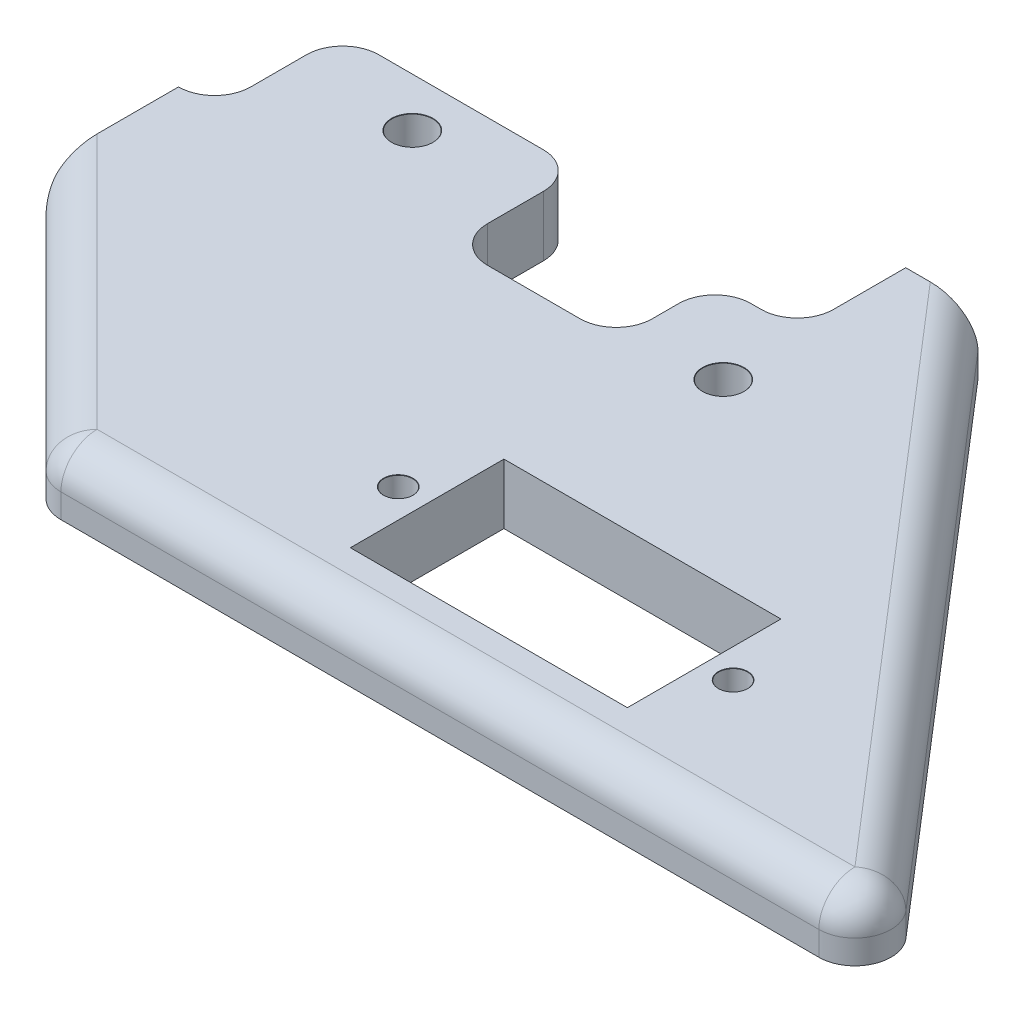
SolidWorks part; units mm, degrees
ref_plane "Front Plane" through (0, 0, 0) normal (0, 0, 1) x (1, 0, 0)
ref_plane "Top Plane" through (0, 0, 0) normal (0, 1, 0) x (1, 0, 0)
ref_plane "Right Plane" through (0, 0, 0) normal (1, 0, 0) x (0, 0, -1)
sketch "Sketch1" plane through (0, 0, 0) normal (0, 1, 0) x (1, 0, 0)
  line L0 (6.83, 0) -> (-6.83, 0)
  line L1 (-9.83, -3) -> (-9.83, -7.63)
  line L2 (9.83, -3) -> (9.83, -7.63)
  line L3 (-12.83, -7.63) -> (-9.83, -7.63) construction
  line L4 (12.83, -7.63) -> (9.83, -7.63) construction
  line L5 (-12.83, -10.63) -> (-12.83, -16.63)
  line L6 (12.83, -10.63) -> (12.83, -16.63)
  line L7 (-12.83, -16.63) -> (12.83, -16.63)
  arc A0 (-6.83, 0) -> (-9.83, -3) centre (-6.83, -3) ccw
  arc A1 (9.83, -3) -> (6.83, 0) centre (6.83, -3) ccw
  arc A2 (-12.83, -10.63) -> (-9.83, -7.63) centre (-12.83, -7.63) ccw
  arc A3 (9.83, -7.63) -> (12.83, -10.63) centre (12.83, -7.63) ccw
  point P4 (0, 0)
  dimension "D4" = 13.66
  dimension "D1" = 3
  dimension "D2" = 6
  dimension "D3" = 13.66
  dimension "D5" = 4.63
extrude "Boss-Extrude1" add sketch "Sketch1" along normal blind 5
sketch "Sketch2" plane through (0, 5, 0) normal (0, 1, 0) x (1, 0, 0)
  line L0 (-12.83, -16.63) -> (-12.83, -23.63)
  line L1 (-12.83, -23.63) -> (54.3469, -41.63)
  line L2 (54.3469, -41.63) -> (54.3469, -16.63)
  line L3 (54.3469, -16.63) -> (12.83, -16.63)
  line L4 (-12.83, -16.63) -> (12.83, -16.63) construction
  line L5 (-12.83, -16.63) -> (12.83, -16.63)
  dimension "D1" = 25
  dimension "D2" = 7
  dimension "D3" = 75
extrude "Boss-Extrude2" [suppressed] add sketch "Sketch2" against normal up to surface (127 mm away) up to face at (0, 0, 7.578)
sketch "Sketch9" plane through (0, 5, 0) normal (0, 1, 0) x (1, 0, 0)
  line L0 (12.83, -16.63) -> (12.83, -10.63) construction
  line L1 (12.83, -16.63) -> (12.83, -10.63)
  line L2 (12.83, -10.63) -> (20.51, -10.63)
  line L3 (23.51, -7.63) -> (23.51, -5.44)
  line L4 (26.51, -2.44) -> (27.36, -2.44)
  line L5 (30.36, 0.56) -> (30.36, 6.56)
  line L6 (12.83, -16.63) -> (36.36, -16.63)
  line L7 (36.36, -16.63) -> (36.36, 6.56)
  line L8 (36.36, 6.56) -> (30.36, 6.56)
  arc A0 (27.36, -2.44) -> (30.36, 0.56) centre (27.36, 0.56) ccw
  arc A1 (23.51, -5.44) -> (26.51, -2.44) centre (26.51, -5.44) cw
  arc A2 (20.51, -10.63) -> (23.51, -7.63) centre (20.51, -7.63) ccw
  dimension "D1" = 3
  dimension "D2" = 7.68
  dimension "D3" = 2.19
  dimension "D4" = 6
  dimension "D5" = 0.85
  dimension "D6" = 6
extrude "Boss-Extrude3" add sketch "Sketch9" against normal up to surface (5 mm away) up to face at (0, 0, 7.578)
hole_wizard "M3 Clearance Hole2" positions "Sketch7" profile "Sketch8" hole size "M3" standard "ANSI Metric" end condition through all
sketch "Sketch7" plane through (0, 5, 0) normal (0, 1, 0) x (1, 0, 0)
  line L0 (0, -4.05) -> (0, 0) construction
  line L1 (29.4813, -1.5613) -> (30.8213, -1.5613) construction
  line L2 (30.8213, -1.5613) -> (30.8213, -9.0513) construction
  arc A0 (27.36, -2.44) -> (30.36, 0.56) centre (27.36, 0.56) ccw construction
  arc A1 (27.36, -2.44) -> (30.36, 0.56) centre (27.36, 0.56) ccw construction
  point P0 (0, -4.05)
  point P5 (30.8213, -9.0513)
  dimension "D1" = 4.05
  dimension "D2" = 1.34
  dimension "D3" = 7.49
sketch "Sketch8" plane through (0, 5, 4.05) normal (1, 0, 0) x (0, 0, 1)
  line L0 (0, 0) -> (0, 5)
  line L1 (0, 5) -> (1.7, 5)
  line L2 (1.7, 5) -> (1.7, 0.025)
  line L3 (1.7, 0.025) -> (1.725, 0)
  line L5 (1.725, 0) -> (0, 0)
  line L6 (-1.7, 0.025) -> (-1.725, 0) construction
  line L11 (0, -6.35) -> (0, 107.95) construction
  dimension "Thru Hole Dia." = 3.4
  dimension "Thru Hole Depth" = 5
  dimension "Near C'Sink Dia." = 3.45
  dimension "Near C'Sink Angle" = 90
sketch "Sketch10" plane through (0, 5, 0) normal (0, 1, 0) x (1, 0, 0)
  line L0 (0, -4.05) -> (38.94, -4.05) construction
  line L1 (38.94, -4.05) -> (77.88, -4.05) construction
  line L2 (-12.83, -16.63) -> (-12.83, -41.63)
  line L3 (-12.83, -41.63) -> (77.88, -41.63)
  line L4 (36.36, 6.56) -> (77.88, 6.56)
  line L5 (-12.83, -16.63) -> (36.36, -16.63) construction
  line L6 (36.36, -16.63) -> (36.36, 6.56) construction
  line L7 (36.36, -16.63) -> (36.36, 6.56)
  line L8 (-12.83, -16.63) -> (36.36, -16.63)
  line L9 (77.88, 6.56) -> (77.88, -41.63)
  point P7 (0, 0)
  point P9 (-18.83, -47.63)
  dimension "D1" = 38.94
  dimension "D2" = 25
extrude "Boss-Extrude4" add sketch "Sketch10" against normal up to surface (5 mm away) up to face at (0, 0, 5.75)
sketch "Sketch11" plane through (0, 5, 0) normal (0, 1, 0) x (1, 0, 0)
  line L0 (-12.83, -16.63) -> (77.88, -16.63) construction
  line L1 (-12.83, -10.63) -> (-12.83, -41.63) construction
  line L2 (77.88, -41.63) -> (77.88, 6.56) construction
  line L3 (0, -4.05) -> (38.94, -4.05) construction
  line L4 (50.44, -23.88) -> (27.44, -23.88)
  line L5 (50.44, -23.88) -> (50.44, -36.63)
  line L6 (50.44, -36.63) -> (27.44, -36.63)
  line L7 (27.44, -23.88) -> (27.44, -36.63)
  line L8 (50.44, -23.88) -> (27.44, -36.63) construction
  line L9 (50.44, -36.63) -> (27.44, -23.88) construction
  line L10 (38.94, -4.05) -> (38.94, -30.255) construction
  line L11 (-12.83, -41.63) -> (77.88, -41.63) construction
  circle A0 centre (0, -4.05) radius 1.725 construction
  circle A1 centre (0, -4.05) radius 1.725 construction
  point P6 (38.94, -30.255)
  dimension "D1" = 6
  dimension "D2" = 38.94
  dimension "D3" = 23
  dimension "D4" = 12.75
  dimension "D5" = 5
extrude "Cut-Extrude1" cut sketch "Sketch11" against normal up to surface (5 mm away) up to face at (0, 0, 5.75)
hole_wizard "M2 Clearance Hole1" positions "Sketch12" profile "Sketch13" hole size "M2" standard "ANSI Metric" end condition through all
sketch "Sketch12" plane through (0, 5, 0) normal (0, 1, 0) x (1, 0, 0)
  line L0 (27.44, -23.88) -> (27.44, -36.63) construction
  line L1 (27.44, -23.88) -> (27.44, -36.63) construction
  line L2 (25.04, -30.255) -> (52.84, -30.255) construction
  line L3 (50.44, -23.88) -> (27.44, -23.88) construction
  line L4 (50.44, -23.88) -> (27.44, -23.88) construction
  point P0 (25.04, -30.255)
  point P2 (52.84, -30.255)
  point P6 (27.44, -30.255)
  point P12 (38.94, -30.255)
  point P13 (38.94, -23.88)
  dimension "D1" = 27.8
sketch "Sketch13" plane through (25.04, 5, 30.255) normal (1, 0, 0) x (0, 0, 1)
  line L0 (0, 0) -> (0, 5)
  line L1 (0, 5) -> (1.2, 5)
  line L2 (1.2, 5) -> (1.2, 0.025)
  line L3 (1.2, 0.025) -> (1.225, 0)
  line L5 (1.225, 0) -> (0, 0)
  line L6 (-1.2, 0.025) -> (-1.225, 0) construction
  line L11 (0, -6.35) -> (0, 107.95) construction
  dimension "Thru Hole Dia." = 2.4
  dimension "Thru Hole Depth" = 5
  dimension "Near C'Sink Dia." = 2.45
  dimension "Near C'Sink Angle" = 90
sketch "Sketch14" plane through (0, 5, 0) normal (0, 1, 0) x (1, 0, 0)
  line L0 (-12.83, -21.63) -> (7.17, -41.63)
  line L1 (-12.83, -10.63) -> (-12.83, -41.63) construction
  line L2 (-12.83, -41.63) -> (77.88, -41.63) construction
  line L3 (7.17, -41.63) -> (-12.83, -41.63)
  line L4 (-12.83, -41.63) -> (-12.83, -21.63)
  line L5 (36.36, 6.56) -> (77.88, -41.63)
  line L6 (77.88, 6.56) -> (30.36, 6.56) construction
  line L7 (77.88, -41.63) -> (77.88, 6.56) construction
  line L8 (36.36, 6.56) -> (77.88, 6.56)
  line L9 (77.88, 6.56) -> (77.88, -41.63)
  dimension "D1" = 11
  dimension "D2" = 45
  dimension "D3" = 6
extrude "Cut-Extrude2" cut sketch "Sketch14" against normal up to surface (5 mm away) up to face at (25.04, 0, 31.455)
fillet "Fillet1" radius 3 2 edges at (-12.83, 2.5, 21.63) (-2.83, 5, 31.63)
fillet "Fillet2" radius 3 3 edges at (7.17, 1, 41.63) (8.4126, 4.1213, 41.63) (44.6463, 5, 41.63)
fillet "Fillet3" radius 3 3 edges at (77.88, 1, 41.63) (77.1229, 4.1213, 40.7513) (55.8276, 5, 16.035)
